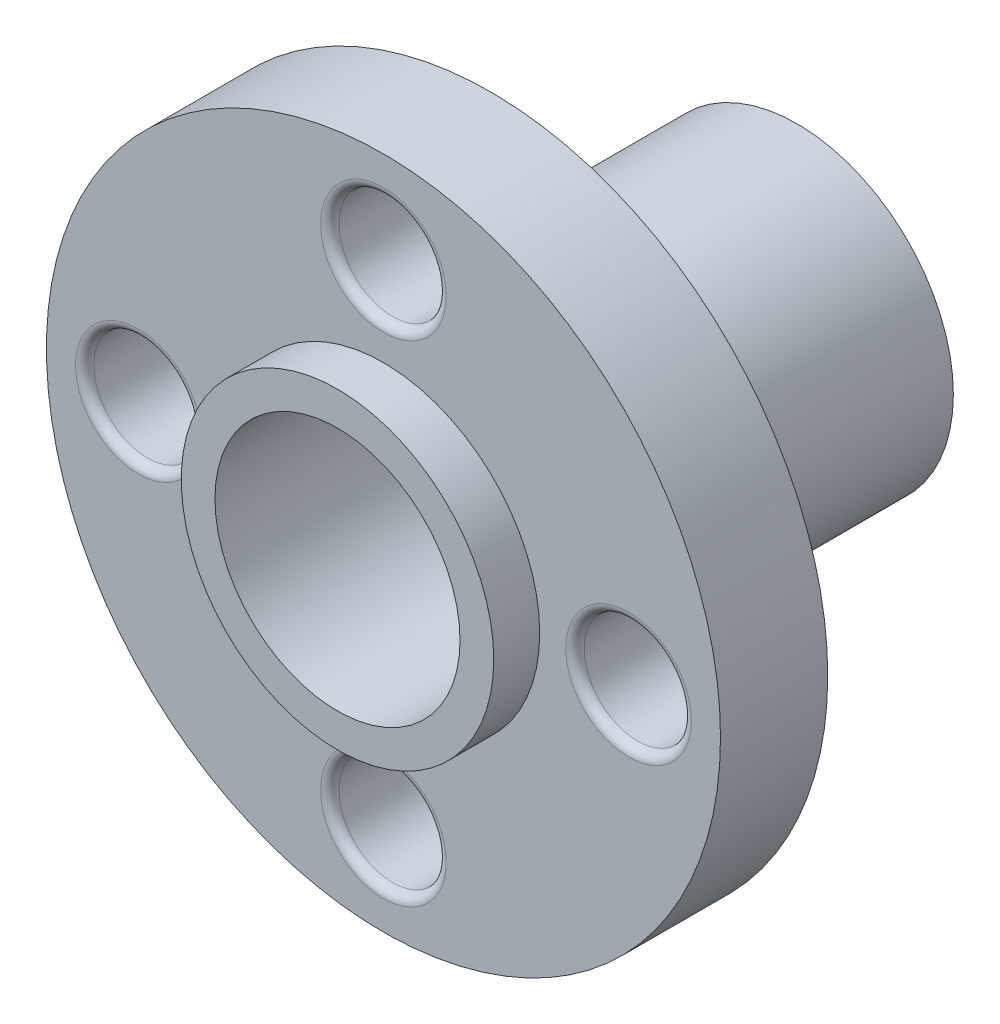
SolidWorks part; units mm, degrees
material "Brass"
ref_plane "Front Plane" through (0, 0, 0) normal (0, 0, 1) x (1, 0, 0)
ref_plane "Top Plane" through (0, 0, 0) normal (0, 1, 0) x (1, 0, 0)
ref_plane "Right Plane" through (0, 0, 0) normal (1, 0, 0) x (0, 0, -1)
sketch "Sketch1" plane through (0, 0, 0) normal (0, 0, 1) x (1, 0, 0)
  circle A0 centre (0, 0) radius 11
  circle A1 centre (0, 0) radius 5.1
  circle A2 centre (0, 0) radius 8 construction
  circle A3 centre (0, 8) radius 1.75
  circle A4 centre (8, 0) radius 1.75
  circle A5 centre (0, -8) radius 1.75
  circle A6 centre (-8, 0) radius 1.75
  point P16 (0, 0)
  dimension "D1" = 22
  dimension "D2" = 10.2
  dimension "D3" = 16
  dimension "D4" = 3.5
  dimension "D5" = 4
extrude "Boss-Extrude1" add sketch "Sketch1" against normal blind 3.5
sketch "Sketch2" plane through (0, 0, 0) normal (0, 0, 1) x (1, 0, 0)
  circle A0 centre (0, 0) radius 5.1
  circle A1 centre (0, 0) radius 4
  dimension "D1" = 8
extrude "Boss-Extrude2" add sketch "Sketch2" along normal blind 1.5 and the other way blind 13.5
sketch "Sketch3" [suppressed] plane through (0, 0, 1.5) normal (0, 0, 1) x (1, 0, 0)
  circle A0 centre (0, 0) radius 4
curve "Helix/Spiral1" [suppressed] pitch 2 height 15 turns 7.5
sketch "Sketch4" plane through (0, 0, 0) normal (0, 1, 0) x (1, 0, 0)
  line L0 (3, -0.55) -> (3, -2.45)
  line L1 (3, -2.45) -> (5, -1.7146)
  line L2 (5, -1.7146) -> (5, -1.2854)
  line L3 (5, -1.2854) -> (3, -0.55)
  line L4 (3, -1.5) -> (5, -1.5)
  point P6 (4, -1.5)
  dimension "D1" = 1.9
  dimension "D2" = 2
  dimension "D3" = 69.811
sweep "Cut-Sweep1" [suppressed] cut profiles "Sketch4" path "Helix/Spiral1"
fillet "Fillet2" radius 0.3 4 edges at (9.75, 0, 0) (1.75, -8, 0) (-6.25, 0, 0) (1.75, 8, 0)
